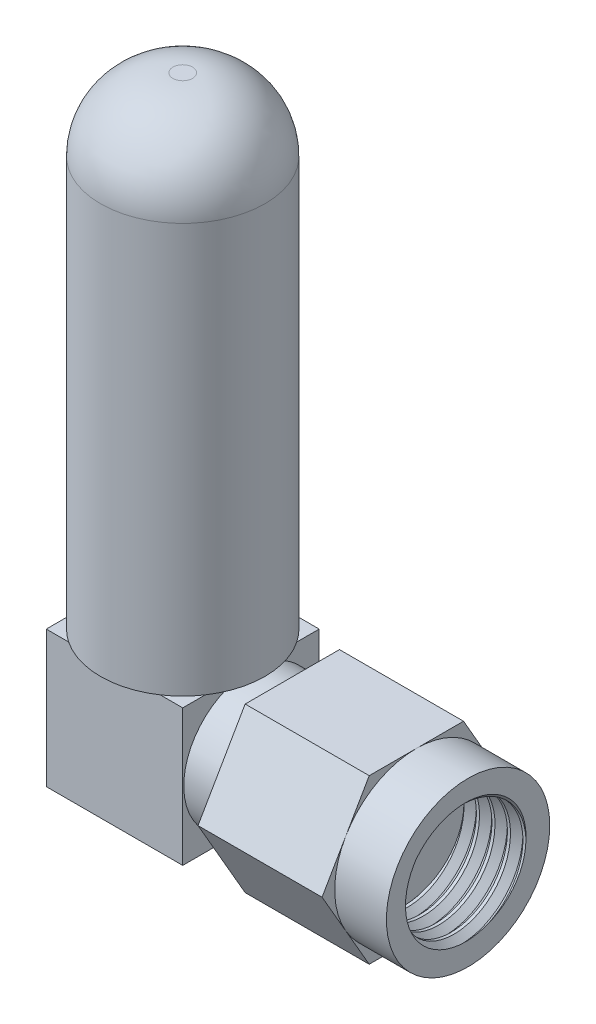
SolidWorks part; units mm, degrees
material "ABS"
ref_plane "Front Plane" through (0, 0, 0) normal (0, 0, 1) x (1, 0, 0)
ref_plane "Top Plane" through (0, 0, 0) normal (0, 1, 0) x (1, 0, 0)
ref_plane "Right Plane" through (0, 0, 0) normal (1, 0, 0) x (0, 0, -1)
sketch "Sketch1" plane through (0, 0, 0) normal (0, 0, 1) x (1, 0, 0)
  line L1 (-3.3, 3.3) -> (3.3, 3.3)
  line L2 (-3.3, 3.3) -> (-3.3, -3.3)
  line L3 (-3.3, -3.3) -> (3.3, -3.3)
  line L4 (3.3, 3.3) -> (3.3, -3.3)
  line L5 (-3.3, 3.3) -> (3.3, -3.3) construction
  line L6 (-3.3, -3.3) -> (3.3, 3.3) construction
  point P0 (0, 0)
  dimension "D1" = 6.6
extrude "Boss-Extrude1" add sketch "Sketch1" along normal mid plane 6.6
sketch "Sketch2" plane through (3.3, 0, 0) normal (1, 0, 0) x (0, 0, -1)
  circle A0 centre (0, 0) radius 3.25
  dimension "D1" = 6.5
extrude "Boss-Extrude2" add sketch "Sketch2" along normal blind 2
sketch "Sketch3" plane through (5.3, 0, 0) normal (1, 0, 0) x (0, 0, -1)
  line L1 (4.5611, 0) -> (2.2805, 3.95)
  line L2 (2.2805, 3.95) -> (-2.2805, 3.95)
  line L3 (-2.2805, 3.95) -> (-4.5611, 0)
  line L4 (-4.5611, 0) -> (-2.2805, -3.95)
  line L5 (-2.2805, -3.95) -> (2.2805, -3.95)
  line L6 (2.2805, -3.95) -> (4.5611, 0)
  circle A0 centre (0, 0) radius 3.95 construction
  dimension "D1" = 7.9
extrude "Boss-Extrude3" add sketch "Sketch3" along normal blind 6
sketch "Sketch4" plane through (11.3, 0, 0) normal (1, 0, 0) x (0, 0, -1)
  line L0 (-2.2805, -3.95) -> (2.2805, -3.95) construction
  circle A0 centre (0, 0) radius 3.95
extrude "Boss-Extrude4" add sketch "Sketch4" along normal blind 2.5
sketch "Sketch5" plane through (13.8, 0, 0) normal (1, 0, 0) x (0, 0, -1)
  circle A0 centre (0, 0) radius 2.8
  dimension "D1" = 5.6
extrude "Cut-Extrude1" cut sketch "Sketch5" against normal blind 3
sketch "Sketch6" plane through (0, 3.3, 0) normal (0, 1, 0) x (1, 0, 0)
  circle A0 centre (0, 0) radius 3.975
  dimension "D1" = 7.95
extrude "Boss-Extrude5" add sketch "Sketch6" along normal blind 23.3
fillet "Fillet1" radius 3.5 1 edges at (-3.975, 26.6, 0)
sketch "Sketch8" plane through (10.8, 0, 0) normal (1, 0, 0) x (0, 0, -1)
  circle A0 centre (0, 0) radius 2.8
  dimension "D1" = 5.6
curve "Helix/Spiral1" pitch 0.75 height 6.75 radius 2.8 left hand yes centre (10.8, 0, 0) axis (1, 0, 0) start towards (0, 0, -1)
sketch "Sketch9" plane through (0, 0, 0) normal (0, 1, 0) x (1, 0, 0)
  line L0 (11.4, 2.8) -> (10.8, 2.8)
  line L1 (10.8, 2.8) -> (11.1, 3.1)
  line L2 (11.1, 3.1) -> (11.4, 2.8)
  line L3 (10.8, -2.8) -> (10.8, 2.8) construction
  line L5 (11.1, 3.1) -> (11.1, 2.8) construction
  spline S0 degree 3 poles (10.8, 2.8) (10.8155, 2.8) (10.8469, 2.6542) (10.8937, 2.0314) (10.9406, 1.0994) (10.9875, 0) (11.0344, -1.0994) (11.0812, -2.0314) (11.1281, -2.6542) (11.175, -2.8729) (11.2219, -2.6542) (11.2687, -2.0314) (11.3313, -0.7887) (11.3938, 0.7887) (11.4562, 2.0314) (11.5031, 2.6542) (11.55, 2.8729) (11.5969, 2.6542) (11.6437, 2.0314) (11.7063, 0.7887) (11.7687, -0.7887) (11.8313, -2.0314) (11.8781, -2.6542) (11.925, -2.8729) (11.9719, -2.6542) (12.0188, -2.0314) (12.0813, -0.7887) (12.1438, 0.7887) (12.2063, 2.0314) (12.2531, 2.6542) (12.3, 2.8729) (12.3469, 2.6542) (12.3937, 2.0314) (12.4563, 0.7887) (12.5188, -0.7887) (12.5813, -2.0314) (12.6281, -2.6542) (12.675, -2.8729) (12.7219, -2.6542) (12.7688, -2.0314) (12.8313, -0.7887) (12.8937, 0.7887) (12.9563, 2.0314) (13.0031, 2.6542) (13.05, 2.8729) (13.0969, 2.6542) (13.1438, 2.0314) (13.2063, 0.7887) (13.2688, -0.7887) (13.3313, -2.0314) (13.3781, -2.6542) (13.425, -2.8729) (13.4719, -2.6542) (13.5188, -2.0314) (13.5813, -0.7887) (13.6438, 0.7887) (13.7063, 2.0314) (13.7531, 2.6542) (13.8, 2.8729) (13.8469, 2.6542) (13.8938, 2.0314) (13.9563, 0.7887) (14.0188, -0.7887) (14.0813, -2.0314) (14.1281, -2.6542) (14.175, -2.8729) (14.2219, -2.6542) (14.2688, -2.0314) (14.3313, -0.7887) (14.3937, 0.7887) (14.4563, 2.0314) (14.5031, 2.6542) (14.55, 2.8729) (14.5969, 2.6542) (14.6438, 2.0314) (14.7062, 0.7887) (14.7687, -0.7887) (14.8313, -2.0314) (14.8781, -2.6542) (14.925, -2.8729) (14.9719, -2.6542) (15.0188, -2.0314) (15.0812, -0.7887) (15.1437, 0.7887) (15.2063, 2.0314) (15.2531, 2.6542) (15.3, 2.8729) (15.3469, 2.6542) (15.3938, 2.0314) (15.4563, 0.7887) (15.5188, -0.7887) (15.5813, -2.0314) (15.6281, -2.6542) (15.675, -2.8729) (15.7219, -2.6542) (15.7688, -2.0314) (15.8312, -0.7887) (15.8938, 0.7887) (15.9563, 2.0314) (16.0031, 2.6542) (16.05, 2.8729) (16.0969, 2.6542) (16.1438, 2.0314) (16.2063, 0.7887) (16.2688, -0.7887) (16.3313, -2.0314) (16.3781, -2.6542) (16.425, -2.8729) (16.4719, -2.6542) (16.5188, -2.0314) (16.5813, -0.7887) (16.6437, 0.7887) (16.7063, 2.0314) (16.7531, 2.6542) (16.8, 2.8729) (16.8469, 2.6542) (16.8938, 2.0314) (16.9562, 0.7887) (17.0187, -0.7887) (17.0813, -2.0314) (17.1281, -2.6542) (17.175, -2.8729) (17.2219, -2.6542) (17.2688, -2.0314) (17.3156, -1.0994) (17.3625, 0) (17.4094, 1.0994) (17.4563, 2.0314) (17.5031, 2.6542) (17.5345, 2.8) (17.55, 2.8) knots 0 0 0 0 0.006944 0.013889 0.020833 0.027778 0.034722 0.041667 0.048611 0.055556 0.0625 0.069444 0.076389 0.090278 0.097222 0.104167 0.111111 0.118056 0.125 0.131944 0.145833 0.152778 0.159722 0.166667 0.173611 0.180556 0.1875 0.201389 0.208333 0.215278 0.222222 0.229167 0.236111 0.243056 0.256944 0.263889 0.270833 0.277778 0.284722 0.291667 0.298611 0.3125 0.319444 0.326389 0.333333 0.340278 0.347222 0.354167 0.368056 0.375 0.381944 0.388889 0.395833 0.402778 0.409722 0.423611 0.430556 0.4375 0.444444 0.451389 0.458333 0.465278 0.479167 0.486111 0.493056 0.5 0.506944 0.513889 0.520833 0.534722 0.541667 0.548611 0.555556 0.5625 0.569444 0.576389 0.590278 0.597222 0.604167 0.611111 0.618056 0.625 0.631944 0.645833 0.652778 0.659722 0.666667 0.673611 0.680556 0.6875 0.701389 0.708333 0.715278 0.722222 0.729167 0.736111 0.743056 0.756944 0.763889 0.770833 0.777778 0.784722 0.791667 0.798611 0.8125 0.819444 0.826389 0.833333 0.840278 0.847222 0.854167 0.868056 0.875 0.881944 0.888889 0.895833 0.902778 0.909722 0.923611 0.930556 0.9375 0.944444 0.951389 0.958333 0.965278 0.972222 0.979167 0.986111 0.993056 1 1 1 1 construction
  dimension "D1" = 0.6
  dimension "D2" = 0.3
  dimension "D3" = 0.3
sweep "Cut-Sweep1" cut profiles "Sketch9" path "Helix/Spiral1" align with end faces yes
